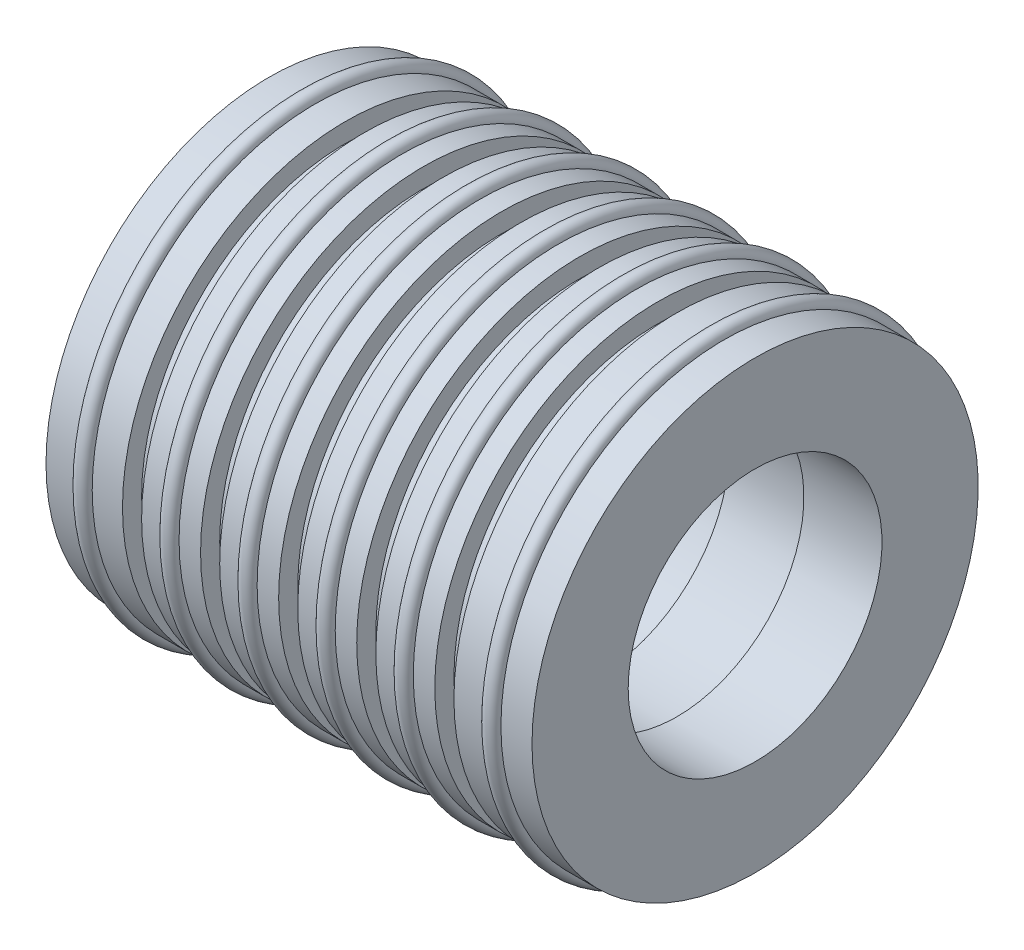
SolidWorks part; units mm, degrees
ref_plane "Front Plane" through (0, 0, 0) normal (0, 0, 1) x (1, 0, 0)
ref_plane "Top Plane" through (0, 0, 0) normal (0, 1, 0) x (1, 0, 0)
ref_plane "Right Plane" through (0, 0, 0) normal (1, 0, 0) x (0, 0, -1)
sketch "Sketch1" plane through (0, 0, 0) normal (0, 0, 1) x (1, 0, 0)
  line L0 (0, 0) -> (36.5459, 0) construction
  line L1 (-7.62, 11.3848) -> (-7.62, 17.78)
  line L3 (31.115, 17.78) -> (31.115, 10.1148)
  line L4 (31.115, 10.1148) -> (24.892, 10.1148)
  line L5 (24.892, 10.1148) -> (24.892, 10.3688)
  line L6 (24.892, 10.3688) -> (18.669, 10.3688)
  line L7 (18.669, 10.3688) -> (18.669, 10.6228)
  line L8 (18.669, 10.6228) -> (12.446, 10.6228)
  line L9 (12.446, 10.6228) -> (12.446, 10.8768)
  line L10 (12.446, 10.8768) -> (6.223, 10.8768)
  line L11 (6.223, 10.8768) -> (6.223, 11.1308)
  line L12 (6.223, 11.1308) -> (0, 11.1308)
  line L13 (0, 11.1308) -> (0, 11.3848)
  line L14 (0, 11.3848) -> (-7.62, 11.3848)
  line L15 (-7.62, 17.78) -> (-5.207, 17.78)
  line L16 (-1.524, 17.78) -> (-1.524, 16.256)
  line L17 (-1.524, 16.256) -> (0, 16.256)
  line L18 (0, 16.256) -> (0, 17.78)
  line L19 (0, 17.78) -> (1.7145, 17.78)
  line L20 (4.699, 17.78) -> (4.699, 16.256)
  line L21 (4.699, 16.256) -> (6.223, 16.256)
  line L22 (6.223, 16.256) -> (6.223, 17.78)
  line L23 (6.223, 17.78) -> (7.9375, 17.78)
  line L24 (10.922, 17.78) -> (10.922, 16.256)
  line L25 (10.922, 16.256) -> (12.446, 16.256)
  line L26 (12.446, 16.256) -> (12.446, 17.78)
  line L27 (12.446, 17.78) -> (14.1605, 17.78)
  line L28 (17.145, 17.78) -> (17.145, 16.256)
  line L29 (17.145, 16.256) -> (18.669, 16.256)
  line L30 (18.669, 16.256) -> (18.669, 17.78)
  line L31 (18.669, 17.78) -> (20.3835, 17.78)
  line L32 (23.368, 17.78) -> (23.368, 16.256)
  line L33 (23.368, 16.256) -> (24.892, 16.256)
  line L34 (24.892, 16.256) -> (24.892, 17.78)
  line L35 (24.892, 17.78) -> (27.3685, 17.78)
  line L36 (-3.937, 17.78) -> (-1.524, 17.78)
  line L37 (2.9845, 17.78) -> (4.699, 17.78)
  line L38 (9.2075, 17.78) -> (10.922, 17.78)
  line L39 (15.4305, 17.78) -> (17.145, 17.78)
  line L40 (21.6535, 17.78) -> (23.368, 17.78)
  line L41 (28.6385, 17.78) -> (31.115, 17.78)
  line L42 (-5.207, 17.78) -> (-3.937, 17.78) construction
  line L43 (1.7145, 17.78) -> (2.9845, 17.78) construction
  line L44 (7.9375, 17.78) -> (9.2075, 17.78) construction
  line L45 (14.1605, 17.78) -> (15.4305, 17.78) construction
  line L46 (20.3835, 17.78) -> (21.6535, 17.78) construction
  line L47 (27.3685, 17.78) -> (28.6385, 17.78) construction
  arc A9 (21.6535, 17.78) -> (20.3835, 17.78) centre (21.0185, 17.78) ccw
  arc A10 (15.4305, 17.78) -> (14.1605, 17.78) centre (14.7955, 17.78) ccw
  arc A11 (9.2075, 17.78) -> (7.9375, 17.78) centre (8.5725, 17.78) ccw
  arc A12 (2.9845, 17.78) -> (1.7145, 17.78) centre (2.3495, 17.78) ccw
  arc A13 (-3.937, 17.78) -> (-5.207, 17.78) centre (-4.572, 17.78) ccw
  arc A14 (28.6385, 17.78) -> (27.3685, 17.78) centre (28.0035, 17.78) ccw
  point P37 (-7.62, 14.5824)
  point P40 (0, 0)
  dimension "D13" = 1.27
  dimension "D1" = 10.1148
  dimension "D2" = 0.254
  dimension "D4" = 17.78
  dimension "D5" = 1.524
  dimension "D6" = 1.524
  dimension "D8" = 1.524
  dimension "D9" = 1.524
  dimension "D10" = 1.524
  dimension "D11" = 1.524
  dimension "D3" = 6.223
  dimension "D7" = 7.62
  dimension "D12" = 38.735
revolve "Revolve1" add sketch "Sketch1" angle 360 about L0
ref_plane "Plane1" through (-0.762, 0, 0) normal (-1, 0, 0) x (0, 0, 1)
ref_plane "Plane2" through (5.461, 0, 0) normal (-1, 0, 0) x (0, 0, 1)
ref_plane "Plane3" through (11.684, 0, 0) normal (1, 0, 0) x (0, 0, -1)
ref_plane "Plane4" through (17.907, 0, 0) normal (-1, 0, 0) x (0, 0, 1)
ref_plane "Plane5" through (24.13, 0, 0) normal (1, 0, 0) x (0, 0, -1)
ref_plane "Plane6" through (0, 17.78, 0) normal (0, 1, 0) x (1, 0, 0)
ref_axis "Axis1" through (0, 0, 0) along (-1, 0, 0)
sketch "Sketch4" plane through (-0.762, 0, 0) normal (-1, 0, 0) x (0, 0, 1)
  point P0 (0, 0)
sketch "Sketch5" plane through (5.461, 0, 0) normal (-1, 0, 0) x (0, 0, 1)
  point P0 (0, 0)
sketch "Sketch6" plane through (11.684, 0, 0) normal (1, 0, 0) x (0, 0, -1)
  point P0 (0, 0)
sketch "Sketch7" plane through (17.907, 0, 0) normal (-1, 0, 0) x (0, 0, 1)
  point P0 (0, 0)
sketch "Sketch8" plane through (24.13, 0, 0) normal (1, 0, 0) x (0, 0, -1)
  point P0 (0, 0)
sketch "Sketch9" plane through (0, 17.78, 0) normal (0, 1, 0) x (1, 0, 0)
  point P0 (24.13, 0)
  point P2 (17.907, 0)
  point P4 (11.684, 0)
  point P6 (5.461, 0)
  point P11 (-0.762, 0)
hole_wizard "#65 (0.035) Diameter Hole1" positions "Sketch9" profile "Sketch10" hole size "#65" standard "ANSI Inch" end condition up to next
sketch "Sketch10" plane through (24.13, 17.78, 0) normal (1, 0, 0) x (0, 0, 1)
  line L0 (0, 0) -> (0, 7.4112)
  line L1 (0, 7.4112) -> (0.4445, 7.4112)
  line L2 (0.4445, 7.4112) -> (0.4445, 0)
  line L5 (0.4445, 0) -> (0, 0)
  line L11 (0, -6.35) -> (0, 107.95) construction
  dimension "Thru Hole Dia." = 0.889
  dimension "Thru Hole Depth" = 7.4112
equation "\"kero_radius\"=0.334in"
equation "\"lox_radius\"=0.23622in"
equation "\"Cavity_width\"=0.031in"
equation "\"tooth_width\"=0.01in"
equation "\"cavity_depth\"=0.031in"
equation "\"seal_step\"=0.01in"
equation "\"purge_length\"=0.04in"
equation "\"D1@Sketch1\"=\"lox_radius\"+\"seal_step\"+\"radial_clearance\"+.15"
equation "\"D2@Sketch1\"=\"seal_step\""
equation "\"insert_radius\" = 0.7in"
equation "\"recycle_groove width\" = 0.06in"
equation "\"D5@Sketch1\"=\"recycle_groove width\""
equation "\"recycle_groove_depth\" = 0.06in"
equation "\"D6@Sketch1\"=\"recycle_groove_depth\""
equation "\"N2_purge_width\"= .06in"
equation "\"N2_purge_depth\"= .06in"
equation "\"drain_width\"= .06in"
equation "\"drain_depth\"= .06in"
equation "\"D9@Sketch1\"=\"drain_depth\""
equation "\"D8@Sketch1\"=\"drain_width\""
equation "\"D10@Sketch1\"=\"N2_purge_depth\""
equation "\"D11@Sketch1\"=\"N2_purge_width\""
equation "\"radial_clearance\"= .002in"
equation "\"D3@Sketch1\"=\"tooth_width\"*5+\"Cavity_width\"*5+\"purge_length\""
equation "\"Insert_Length\"= \"D12@Sketch1\""
equation "\"InsertLength\"= 1.525in"
equation "\"D4@Sketch1\"=\"insert_radius\""
equation "\"bumb_radius\"= 0.05"
equation "\"D13@Sketch1\"=\"bumb_radius\""
